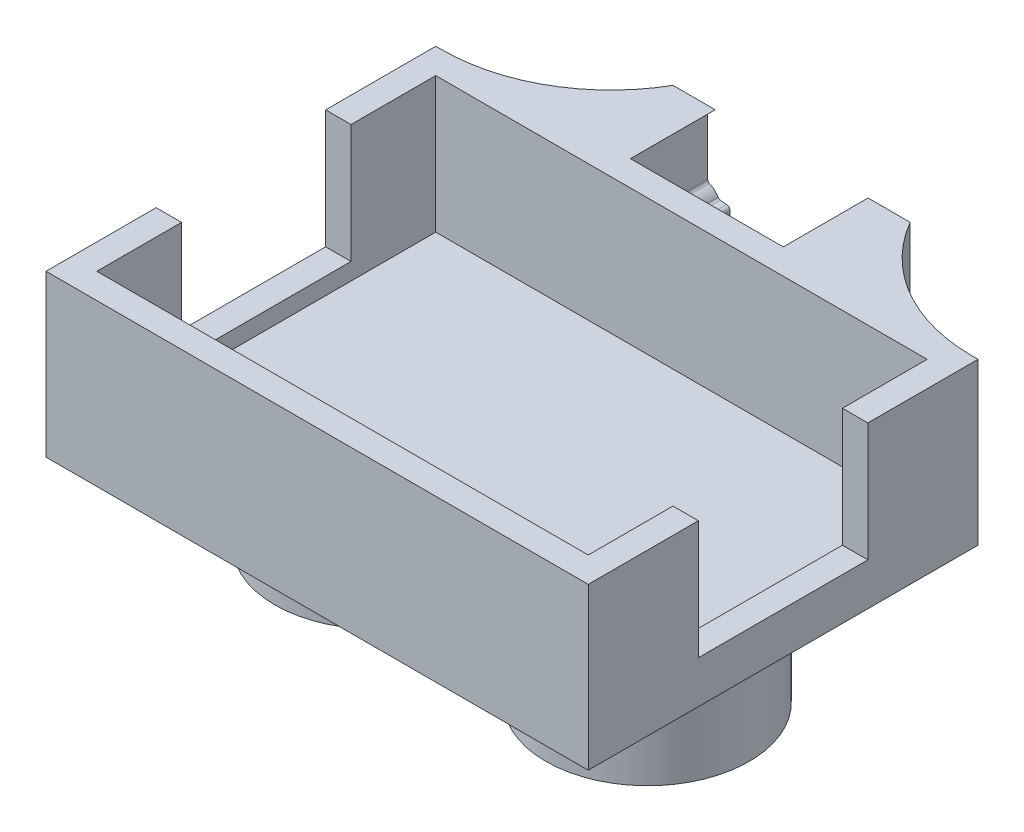
SolidWorks part; units mm, degrees
ref_plane "Front Plane" through (0, 0, 0) normal (0, 0, 1) x (1, 0, 0)
ref_plane "Top Plane" through (0, 0, 0) normal (0, 1, 0) x (1, 0, 0)
ref_plane "Right Plane" through (0, 0, 0) normal (1, 0, 0) x (0, 0, -1)
sketch "Sketch4" plane through (0, 0, 0) normal (0, 1, 0) x (1, 0, 0)
  line L1 (-16, -11.5) -> (16, -11.5)
  line L2 (-16, -11.5) -> (-16, 11.5)
  line L3 (-16, 11.5) -> (16, 11.5)
  line L4 (16, -11.5) -> (16, 11.5)
  line L5 (-16, -11.5) -> (16, 11.5) construction
  line L6 (-16, 11.5) -> (16, -11.5) construction
  point P0 (0, 0)
  dimension "D1" = 32
  dimension "D2" = 23
extrude "Boss-Extrude3" add sketch "Sketch4" along normal blind 9.5
sketch "Sketch5" plane through (0, 9.5, 0) normal (0, 1, 0) x (1, 0, 0)
  line L1 (-14.5, -10) -> (14.5, -10)
  line L2 (-14.5, -10) -> (-14.5, 10)
  line L3 (-14.5, 10) -> (14.5, 10)
  line L4 (14.5, -10) -> (14.5, 10)
  line L5 (-14.5, -10) -> (14.5, 10) construction
  line L6 (-14.5, 10) -> (14.5, -10) construction
  point P0 (0, 0)
  dimension "D1" = 29
  dimension "D2" = 20
extrude "Cut-Extrude2" cut sketch "Sketch5" against normal blind 8
sketch "Sketch8" plane through (-16, 0, 0) normal (-1, 0, 0) x (0, 0, 1)
  line L2 (-11.5, 9.5) -> (11.5, 9.5) construction
  line L4 (11.5, 9.5) -> (11.5, 0) construction
  line L8 (-2.2, 9.5) -> (-1.4, 9.5)
  spline S0 degree 3 poles (-2.2, 9.5) (-2.1353, 9.2413) (-1.5778, 9.0675) (-1.4, 9.5) knots 0 0 0 0 1 1 1 1
  line B0 (4.5, 6.0583) -> (4.5, 9.1)
  line B1 (4.5, 9.1) -> (4.1, 9.5)
  line B2 (4.1, 9.5) -> (-1.4, 9.5)
  line B3 (-2.2, 9.5) -> (-4.1, 9.5)
  line B4 (-4.1, 9.5) -> (-4.5, 9.1)
  line B5 (-4.5, 9.1) -> (-4.5, 6.0583)
  line B6 (-3.8235, 5.4365) -> (-3.4826, 5.4066)
  line B7 (-3.3, 5.2074) -> (-3.3, 4.7926)
  line B8 (-3.4826, 4.5934) -> (-3.8235, 4.5635)
  line B9 (-4.5, 3.9417) -> (-4.5, 3.4)
  line B10 (-4.5, 3.4) -> (-4.1, 3)
  line B11 (-4.1, 3) -> (4.1, 3)
  line B12 (4.1, 3) -> (4.5, 3.4)
  line B13 (4.5, 3.4) -> (4.5, 3.9417)
  line B14 (3.8235, 4.5635) -> (3.4826, 4.5934)
  line B15 (3.3, 4.7926) -> (3.3, 5.2074)
  line B16 (3.4826, 5.4066) -> (3.8235, 5.4365)
  arc B17 (-2.2, 9.5) -> (-1.4, 9.5) centre (-1.8, 9.8) ccw
  arc B18 (-4.5, 6.0583) -> (-4.4087, 5.9203) centre (-4.35, 6.0583) ccw
  arc B19 (-3.9395, 5.5095) -> (-4.4087, 5.9203) centre (-4.8, 5) ccw
  arc B20 (-3.9395, 5.5095) -> (-3.8235, 5.4365) centre (-3.8104, 5.5859) ccw
  arc B21 (-3.3, 5.2074) -> (-3.4826, 5.4066) centre (-3.5, 5.2074) ccw
  arc B22 (-3.4826, 4.5934) -> (-3.3, 4.7926) centre (-3.5, 4.7926) ccw
  arc B23 (-3.8235, 4.5635) -> (-3.9395, 4.4905) centre (-3.8104, 4.4141) ccw
  arc B24 (-4.4087, 4.0797) -> (-3.9395, 4.4905) centre (-4.8, 5) ccw
  arc B25 (-4.4087, 4.0797) -> (-4.5, 3.9417) centre (-4.35, 3.9417) ccw
  arc B26 (4.5, 3.9417) -> (4.4087, 4.0797) centre (4.35, 3.9417) ccw
  arc B27 (3.9395, 4.4905) -> (4.4087, 4.0797) centre (4.8, 5) ccw
  arc B28 (3.9395, 4.4905) -> (3.8235, 4.5635) centre (3.8104, 4.4141) ccw
  arc B29 (3.3, 4.7926) -> (3.4826, 4.5934) centre (3.5, 4.7926) ccw
  arc B30 (3.4826, 5.4066) -> (3.3, 5.2074) centre (3.5, 5.2074) ccw
  arc B31 (3.8235, 5.4365) -> (3.9395, 5.5095) centre (3.8104, 5.5859) ccw
  arc B32 (4.4087, 5.9203) -> (3.9395, 5.5095) centre (4.8, 5) ccw
  arc B33 (4.4087, 5.9203) -> (4.5, 6.0583) centre (4.35, 6.0583) ccw
  line M194 (11.5, 9.5) -> (-11.5, 9.5)
  dimension "D1" = 7
sketch_block_instance "9mm Block-2"
sketch_block "9mm Block"
extrude "Cut-Extrude4" cut sketch "Sketch8" against normal up to surface (32 mm away) contours B32 B33 B0 B1 S0 B4 B5 B18 B19 B20 B6 B21 B7 B22 B8 B23 B24 B25 B9 B10 B11 B12 B13 B26 B27 B28 B14 B29 B15 B30 B16 B31 M194 | B17 M194 | B17 S0 region at (-16, 9.2916, -1.8) region at (-16, 6.3052, 0.005) region at (-16, 9.4184, -1.8) up to face at (16, 4.75, 0)
sketch "Sketch9" plane through (0, 0, 0) normal (0, -1, 0) x (-1, 0, 0)
  line L0 (16, -11.5) -> (-16, -11.5) construction
  line L1 (0, -11.5) -> (0, 11.5) construction
  line L2 (-16, 11.5) -> (16, 11.5) construction
  line L3 (0, -11.5) -> (16, 11.5) construction
  line L4 (16, -11.5) -> (0, 11.5) construction
  circle A0 centre (8, 0) radius 4.8387
  circle A1 centre (8, 0) radius 6
  circle A2 centre (-8, 0) radius 4.8387
  circle A3 centre (-8, 0) radius 6
  dimension "D1" = 9.6774
  dimension "D2" = 12
extrude "Boss-Extrude5" add sketch "Sketch9" along normal blind 3.302 contours A1 | A3 | A2 | A0
sketch "Sketch10" plane through (0, -3.302, 0) normal (0, -1, 0) x (-1, 0, 0)
  line L0 (0, -11.5) -> (0, 11.5) construction
  line L1 (16, -11.5) -> (-16, -11.5) construction
  line L2 (-16, 11.5) -> (16, 11.5) construction
  circle A0 centre (8, 0) radius 6
  circle A1 centre (8, 0) radius 3.6
  circle A2 centre (-8, 0) radius 3.6
  circle A3 centre (-8, 0) radius 6
  dimension "D1" = 12
  dimension "D2" = 7.2
extrude "Boss-Extrude6" add sketch "Sketch10" along normal blind 3
sketch "Sketch12" plane through (-16, 0, 0) normal (-1, 0, 0) x (0, 0, 1)
  line L0 (4.1, 9.5) -> (11.5, 9.5) construction
  line L5 (-5, 2.5) -> (5, 2.5)
  line L6 (-5, 2.5) -> (-5, 9.5)
  line L7 (-5, 9.5) -> (5, 9.5)
  line L8 (5, 2.5) -> (5, 9.5)
  line L9 (-5, 2.5) -> (5, 9.5) construction
  line L10 (-5, 9.5) -> (5, 2.5) construction
  line L11 (11.5, 9.5) -> (11.5, 0) construction
  point P4 (0, 6)
  dimension "D1" = 10
  dimension "D2" = 7
  dimension "D3" = 6.5
extrude "Cut-Extrude5" cut sketch "Sketch12" against normal up to surface (32 mm away) up to face at (16, 5.25, 0)
sketch "Sketch15" plane through (0, 0, -11.5) normal (0, 0, -1) x (-1, 0, 0)
  line L0 (-16, 9.5) -> (16, 9.5) construction
  line L1 (-16, 0) -> (16, 0) construction
  line L2 (16, 9.5) -> (16, 0) construction
  line L3 (-7, 9.5) -> (7, 9.5)
  line L4 (-7, 9.5) -> (-7, 0)
  line L5 (-7, 0) -> (7, 0)
  line L6 (7, 9.5) -> (7, 0)
  line L7 (-7, 9.5) -> (7, 0) construction
  line L8 (-7, 0) -> (7, 9.5) construction
  point P8 (0, 2.35)
  point P14 (0, 4.75)
  line B0 (4.95, 5.7141) -> (4.95, 9.06)
  line B1 (4.95, 9.06) -> (4.51, 9.5)
  line B2 (4.51, 9.5) -> (-1.54, 9.5)
  line B3 (-2.42, 9.5) -> (-4.51, 9.5)
  line B4 (-4.51, 9.5) -> (-4.95, 9.06)
  line B5 (-4.95, 9.06) -> (-4.95, 5.7141)
  line B6 (-4.2059, 5.0301) -> (-3.8308, 4.9973)
  line B7 (-3.63, 4.7781) -> (-3.63, 4.3219)
  line B8 (-3.8308, 4.1027) -> (-4.2059, 4.0699)
  line B9 (-4.95, 3.3859) -> (-4.95, 2.79)
  line B10 (-4.95, 2.79) -> (-4.51, 2.35)
  line B11 (-4.51, 2.35) -> (4.51, 2.35)
  line B12 (4.51, 2.35) -> (4.95, 2.79)
  line B13 (4.95, 2.79) -> (4.95, 3.3859)
  line B14 (4.2059, 4.0699) -> (3.8308, 4.1027)
  line B15 (3.63, 4.3219) -> (3.63, 4.7781)
  line B16 (3.8308, 4.9973) -> (4.2059, 5.0301)
  arc B17 (-2.42, 9.5) -> (-1.54, 9.5) centre (-1.98, 9.83) ccw
  arc B18 (-4.95, 5.7141) -> (-4.8496, 5.5623) centre (-4.785, 5.7141) ccw
  arc B19 (-4.3335, 5.1104) -> (-4.8496, 5.5623) centre (-5.28, 4.55) ccw
  arc B20 (-4.3335, 5.1104) -> (-4.2059, 5.0301) centre (-4.1915, 5.1945) ccw
  arc B21 (-3.63, 4.7781) -> (-3.8308, 4.9973) centre (-3.85, 4.7781) ccw
  arc B22 (-3.8308, 4.1027) -> (-3.63, 4.3219) centre (-3.85, 4.3219) ccw
  arc B23 (-4.2059, 4.0699) -> (-4.3335, 3.9896) centre (-4.1915, 3.9055) ccw
  arc B24 (-4.8496, 3.5377) -> (-4.3335, 3.9896) centre (-5.28, 4.55) ccw
  arc B25 (-4.8496, 3.5377) -> (-4.95, 3.3859) centre (-4.785, 3.3859) ccw
  arc B26 (4.95, 3.3859) -> (4.8496, 3.5377) centre (4.785, 3.3859) ccw
  arc B27 (4.3335, 3.9896) -> (4.8496, 3.5377) centre (5.28, 4.55) ccw
  arc B28 (4.3335, 3.9896) -> (4.2059, 4.0699) centre (4.1915, 3.9055) ccw
  arc B29 (3.63, 4.3219) -> (3.8308, 4.1027) centre (3.85, 4.3219) ccw
  arc B30 (3.8308, 4.9973) -> (3.63, 4.7781) centre (3.85, 4.7781) ccw
  arc B31 (4.2059, 5.0301) -> (4.3335, 5.1104) centre (4.1915, 5.1945) ccw
  arc B32 (4.8496, 5.5623) -> (4.3335, 5.1104) centre (5.28, 4.55) ccw
  arc B33 (4.8496, 5.5623) -> (4.95, 5.7141) centre (4.785, 5.7141) ccw
  line M2 (-16, 0) -> (16, 0)
  line M4 (16, 9.5) -> (-16, 9.5)
  dimension "D1" = 14
  dimension "D2" = 9
sketch_block_instance "9mm Block-7"
extrude "Boss-Extrude7" add sketch "Sketch15" along normal blind 5 contours B33 B32 B31 B16 B30 B15 B29 B14 B28 B27 B26 B13 B12 B11 B10 B9 B25 B24 B23 B8 B22 B7 B21 B6 B20 B19 B18 B5 B4 L4 L6 B1 B0 M4 M2 region at (5.755, 9.3308, -11.5)
fillet "Fillet1" radius 10 2 edges at (-7, 4.75, -11.5) (7, 4.75, -11.5)
